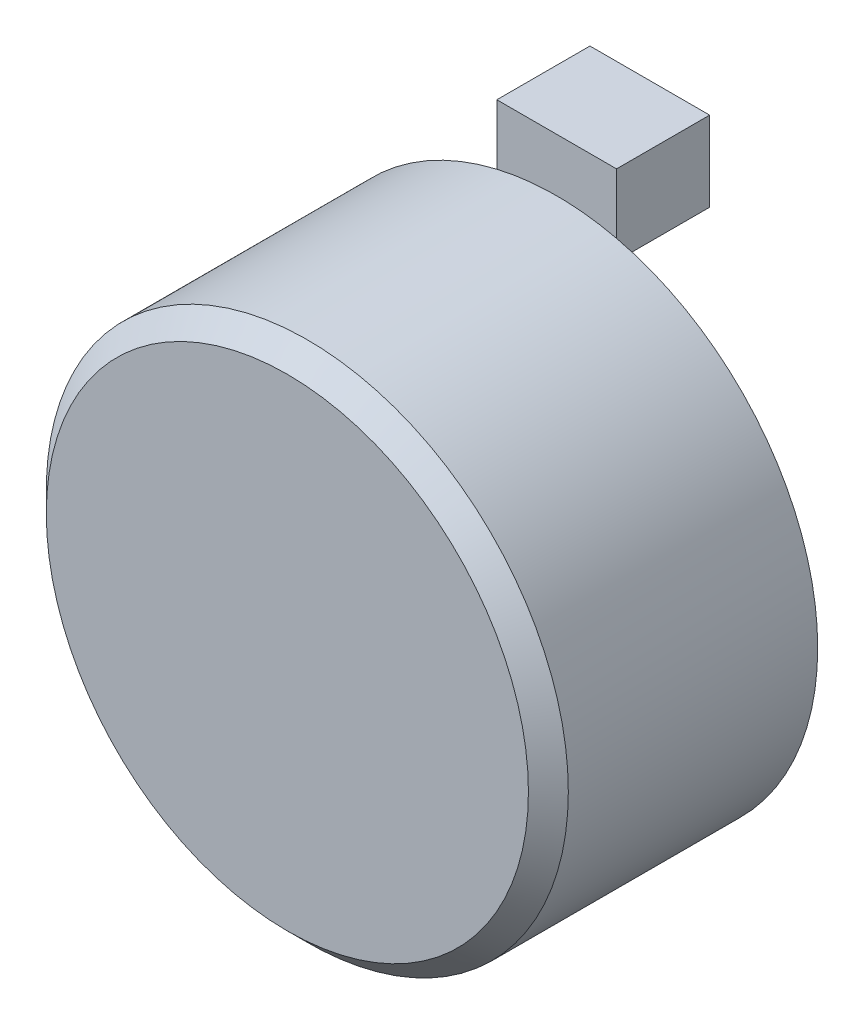
SolidWorks part; units mm, degrees
ref_plane "Front Plane" through (0, 0, 0) normal (0, 0, 1) x (1, 0, 0)
ref_plane "Top Plane" through (0, 0, 0) normal (0, 1, 0) x (1, 0, 0)
ref_plane "Right Plane" through (0, 0, 0) normal (1, 0, 0) x (0, 0, -1)
sketch "SK_Body" plane through (0, 0, 0) normal (0, 1, 0) x (1, 0, 0)
  line L0 (0, -10) -> (0, 50.5) construction
  line L1 (0, 0) -> (36.25, 0)
  line L2 (36.25, 0) -> (39.25, 3)
  line L3 (39.25, 3) -> (39.25, 40.5)
  line L4 (39.25, 40.5) -> (36.25, 40.5)
  line L5 (36.25, 40.5) -> (0, 40.5)
  line L6 (0, 40.5) -> (0, 0)
  dimension "P1" = 10
  dimension "P2" = 50.5
  dimension "R_front" = 36.25
  dimension "P4" = 39.25
  dimension "P5" = 3
  dimension "R_body" = 39.25
  dimension "L_body" = 40.5
  dimension "P8" = 36.25
  dimension "P9" = 40.5
  dimension "P10" = 40.5
revolve "Housing_Body" add sketch "SK_Body" angle 360 about L0
ref_plane "PL_Rear" through (0, 0, -40.5) normal (0, 0, 1) x (1, 0, 0)
sketch "SK_RearHole" plane through (0, 0, -40.5) normal (0, 0, 1) x (1, 0, 0)
  circle A0 centre (33, 0) radius 1.25
  dimension "D_rh" = 2.5
  dimension "R_rh" = 33
extrude "Rear_Tapped_Hole" cut sketch "SK_RearHole" along normal blind 8
ref_axis "AX_Joint" through (0, 0, -57.225) along (0, 0, 1)
pattern_circular "Rear_Hole_Pattern" count 6 over 360 about axis through (0, 0, -57.225) along (0, 0, 1) of "Rear_Tapped_Hole"
sketch "SK_Connector" plane through (0, 0, -40.5) normal (0, 0, 1) x (1, 0, 0)
  line L0 (-9, 35.25) -> (9, 35.25)
  line L1 (9, 35.25) -> (9, 47.25)
  line L2 (9, 47.25) -> (-9, 47.25)
  line L3 (-9, 47.25) -> (-9, 35.25)
  dimension "P1" = 9
  dimension "P2" = 35.25
  dimension "P3" = 9
  dimension "P4" = 35.25
  dimension "P5" = 9
  dimension "P6" = 47.25
  dimension "P7" = 9
  dimension "P8" = 47.25
extrude "Connector_Zone" add sketch "SK_Connector" against normal blind 14
equation "\"D_act\" = 78.5"
equation "\"L_housing\" = 40.5"
equation "\"PCD_rear\" = 66"
equation "\"D_rear_hole\" = 2.5"
equation "\"D_bearing_boss\" = 46"
equation "\"R_front@SK_Body\" = \"D_act\"/2-3.0"
equation "\"R_body@SK_Body\" = \"D_act\"/2"
equation "\"L_body@SK_Body\" = \"L_housing\""
equation "\"D_rh@SK_RearHole\" = \"D_rear_hole\""
equation "\"R_rh@SK_RearHole\" = \"PCD_rear\"/2"
